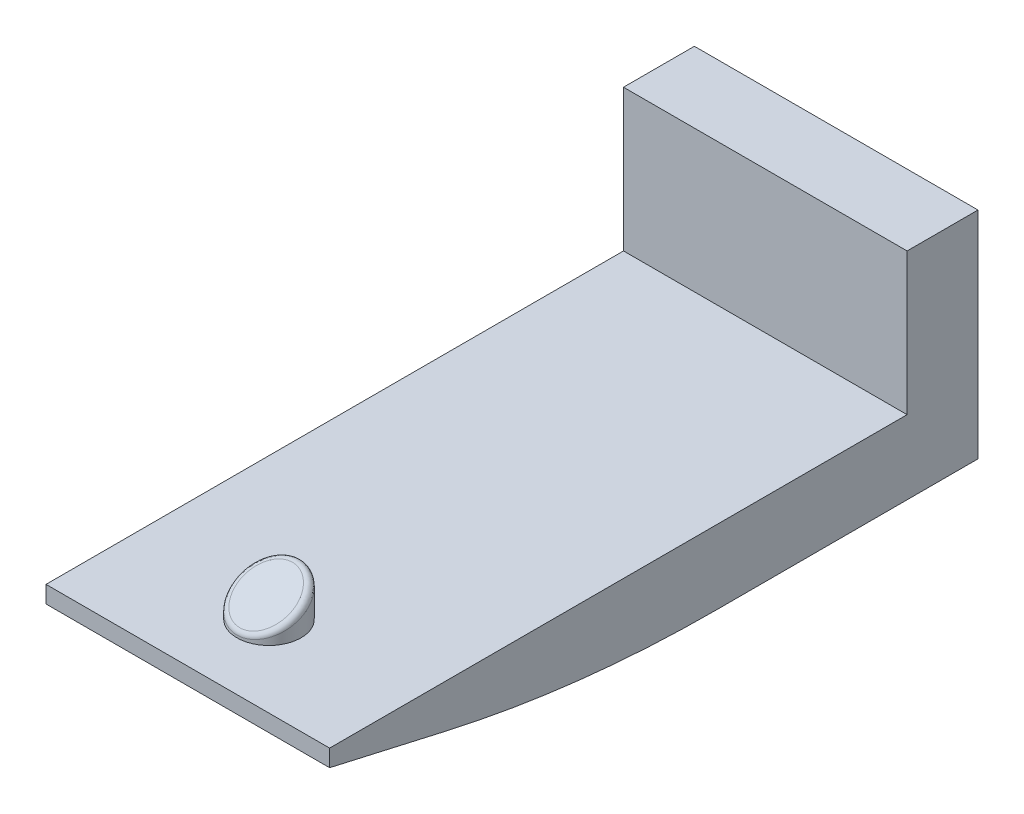
SolidWorks part; units mm, degrees
ref_plane "Front Plane" through (0, 0, 0) normal (0, 0, 1) x (1, 0, 0)
ref_plane "Top Plane" through (0, 0, 0) normal (0, 1, 0) x (1, 0, 0)
ref_plane "Right Plane" through (0, 0, 0) normal (1, 0, 0) x (0, 0, -1)
sketch "Sketch1" plane through (0, 0, 0) normal (1, 0, 0) x (0, 0, -1)
  line L0 (-32.385, 0) -> (0, 0)
  line L1 (0, 0) -> (0, 9.652)
  line L2 (0, 9.652) -> (-3.175, 9.652)
  line L3 (-3.175, 9.652) -> (-3.175, 3.302)
  line L4 (-3.175, 3.302) -> (-32.385, 3.302)
  line L5 (-32.385, 3.302) -> (-32.385, 0)
  line L6 (-29.0357, 3.302) -> (-29.0357, 2.54)
  line L7 (-32.385, 4.8006) -> (-32.385, 1.3716)
  line L8 (-32.385, 1.3716) -> (-23.9, 1.3716)
  line L9 (-23.9, 1.3716) -> (-23.9, 4.8006)
  line L10 (-23.9, 4.8006) -> (-32.385, 4.8006)
  line L11 (-25.4, 3.302) -> (-25.4, 4.8006) construction
  line L12 (-23.9, 4.8006) -> (-23.9, 3.302) construction
  line L13 (-32.385, 3.302) -> (-23.9, 1.3716)
  circle A1 centre (-3.175, 3.302) radius 1.016
  arc A2 (-11.6883, 0) -> (-23.9, 1.3716) centre (-11.6883, 55.0476) cw
  dimension "D5" = 2.032
  dimension "D3" = 3.175
  dimension "D1" = 3.302
  dimension "D2" = 29.21
  dimension "D4" = 6.35
  dimension "D7" = 1.4986
  dimension "D8" = 3.429
  dimension "D10" = 1.5
  dimension "D6" = 0.762
  dimension "D9" = 22.225
extrude "Boss-Extrude1" add sketch "Sketch1" along normal blind 12.7 contours L5 L13 L9 L4 | L1 L2 L3 A1 L4 L9 | L4 A1 L3 region at (0, 2.7545, 9.3516) region at (0, 2.5866, 26.0964) region at (0, 3.1583, 3.0313)
sketch "Sketch2" plane through (0, 3.302, 0) normal (0, 1, 0) x (1, 0, 0)
  line L0 (12.7, -3.175) -> (0, -3.175) construction
  line L4 (12.7, -32.385) -> (0, -32.385) construction
  circle A0 centre (6.35, -25.4) radius 1.4351
  point P5 (6.35, -32.385)
  dimension "D1" = 2.8702
  dimension "D2" = 22.225
extrude "Boss-Extrude2" add sketch "Sketch2" along normal blind 3.81
sketch "Sketch3" plane through (12.7, 0, 0) normal (1, 0, 0) x (0, 0, -1)
  line L0 (-26.8351, 3.556) -> (-23.9649, 5.207)
  line L1 (-23.9649, 3.302) -> (-23.9649, 7.112) construction
  line L2 (-23.9649, 5.207) -> (-23.9649, 7.112)
  line L3 (-23.9649, 7.112) -> (-26.8351, 7.112)
  line L4 (-26.8351, 7.112) -> (-26.8351, 3.556)
  line L5 (-26.8351, 7.112) -> (-26.8351, 3.302) construction
  line L6 (-3.175, 3.302) -> (-32.385, 3.302) construction
  dimension "D1" = 0.254
extrude "Cut-Extrude1" cut sketch "Sketch3" against normal through all contours L4 L0 L2 L3
fillet "Fillet1" radius 0.254 1 edges at (6.35, 3.556, 26.8351)
fillet "Fillet2" [suppressed] radius 1.27
equation "\"WallThickness\"=0.125"
equation "\"D9@Sketch1\"=\"WallThickness\"+.75"
equation "\"D2@Sketch2\"=\"WallThickness\"+.75"
